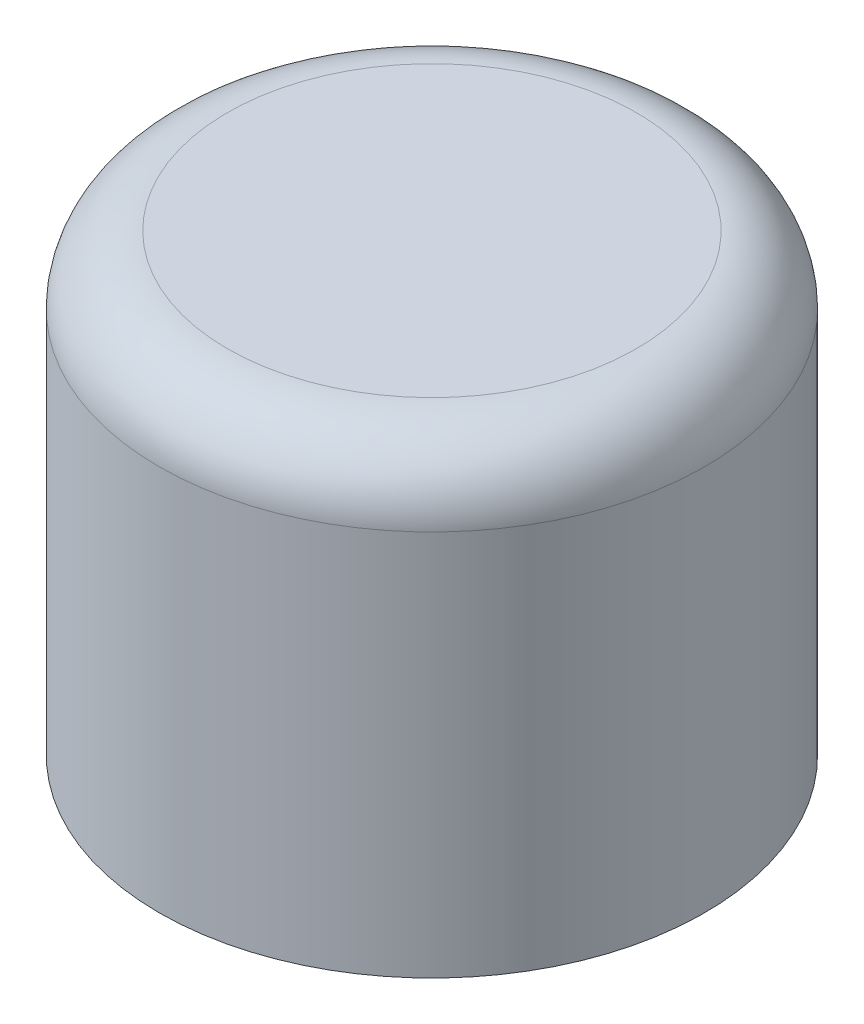
SolidWorks part; units mm, degrees
ref_plane "Front Plane" through (0, 0, 0) normal (0, 0, 1) x (1, 0, 0)
ref_plane "Top Plane" through (0, 0, 0) normal (0, 1, 0) x (1, 0, 0)
ref_plane "Right Plane" through (0, 0, 0) normal (1, 0, 0) x (0, 0, -1)
sketch "Sketch1" plane through (0, 0, 0) normal (0, 1, 0) x (1, 0, 0)
  line L0 (0, 6) -> (0, 0) construction
  line L1 (0, 0) -> (0, 3) construction
  line L2 (0, 3) -> (-0.4, 3) construction
  line L3 (0, 3) -> (0.4, 3) construction
  line L5 (-0.4, 5.9867) -> (0.4, 5.9867)
  line L6 (-0.4, 5.9867) -> (-0.4, -5.9867)
  line L7 (-0.4, -5.9867) -> (0.4, -5.9867)
  line L8 (0.4, 5.9867) -> (0.4, -5.9867)
  circle A0 centre (0, 0) radius 6
  circle A1 centre (0, 0) radius 5.25
  dimension "D1" = 12
  dimension "D4" = 10.5
  dimension "D2" = 0.4
  dimension "D3" = 0.4
extrude "Boss-Extrude1" add sketch "Sketch1" along normal blind 8 contours L6 L7 L8 L5 | A1 | A0
sketch "Sketch4" plane through (0, 8, 0) normal (0, 1, 0) x (1, 0, 0)
  circle A0 centre (0, 0) radius 6
extrude "Boss-Extrude2" add sketch "Sketch4" along normal blind 2
fillet "Fillet1" radius 1.5 1 edges at (0, 10, 6)
